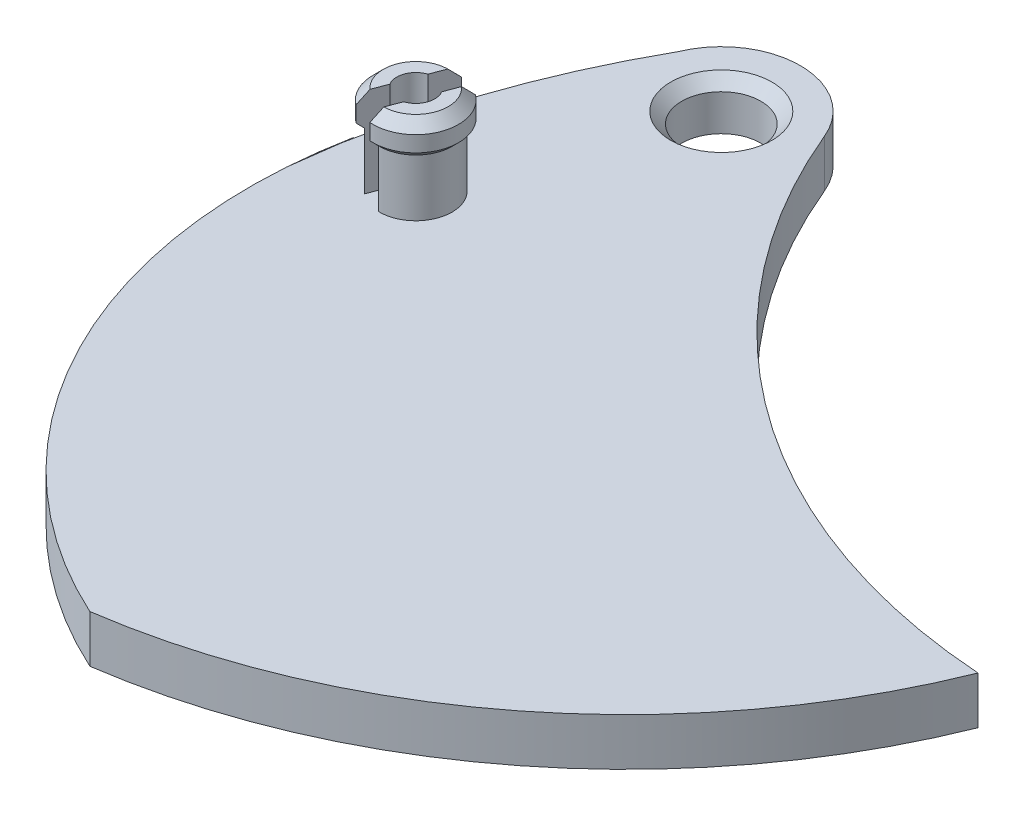
SolidWorks part; units mm, degrees
ref_plane "Front Plane" through (0, 0, 0) normal (0, 0, 1) x (1, 0, 0)
ref_plane "Top Plane" through (0, 0, 0) normal (0, 1, 0) x (1, 0, 0)
ref_plane "Right Plane" through (0, 0, 0) normal (1, 0, 0) x (0, 0, -1)
sketch "Sketch1" plane through (0, 0, 0) normal (0, 1, 0) x (1, 0, 0)
  line L5 (36.4058, -26.4503) -> (51.1392, -23.6349) construction
  line L6 (36.4058, 26.4503) -> (25.6898, 36.9464) construction
  line L7 (-9.9393, 38.7454) -> (25.6898, 36.9464) construction
  line L8 (-45, 0) -> (-50.2845, -14.0383) construction
  line L9 (0, 0) -> (25.6898, 36.9464) construction
  line L10 (-50.2845, -14.0383) -> (-37.5654, -47.3684) construction
  line L11 (-6.1164, -22.6509) -> (-50.2845, -14.0383) construction
  line L12 (51.1392, -23.6349) -> (35.4442, 18.5394) construction
  line L13 (51.1392, -23.6349) -> (72.9384, 4.6045) construction
  line L14 (51.1392, -23.6349) -> (45.5911, -53.1174) construction
  line L15 (-69.4092, 9.0754) -> (-50.2845, -14.0383) construction
  line L16 (-69.4092, 9.0754) -> (0, 0) construction
  line L17 (36.4058, -26.4503) -> (0, 0) construction
  line L18 (36.4058, 26.4503) -> (0, 0) construction
  line L19 (45.5911, -53.1174) -> (0, 0) construction
  line L20 (25.6898, 36.9464) -> (55.0124, 43.2856) construction
  line L21 (55.0124, 43.2856) -> (0, 0) construction
  line L22 (51.1392, -23.6349) -> (34.7485, -11.7263) construction
  line L23 (25.6898, 36.9464) -> (9.2991, 25.0379) construction
  circle A12 centre (25.6898, 36.9464) radius 2.5 construction
  circle A15 centre (25.6898, 36.9464) radius 5 construction
  circle A16 centre (-13.9058, 42.7975) radius 2.5
  circle A19 centre (-13.9058, 42.7975) radius 5
  circle A26 centre (0, 0) radius 40
  circle A27 centre (0, 0) radius 50 construction
  circle A28 centre (-45, 0) radius 5
  circle A29 centre (-45, 0) radius 2.5
  arc A38 (-40.3824, 1.9177) -> (-6.1164, -22.6509) centre (-3.4415, 17.2596) ccw
  circle A39 centre (-50.2845, -14.0383) radius 2.5
  circle A40 centre (-50.2845, -14.0383) radius 5
  arc A41 (-6.1164, -22.6509) -> (-37.5654, -47.3684) centre (-43.2469, -7.774) cw
  arc A42 (-55.1921, -13.0814) -> (-37.5654, -47.3684) centre (-24.6254, -19.0417) ccw
  arc A43 (-49.6161, 1.9214) -> (-55.2764, -13.7547) centre (-6.0759, -22.6602) ccw
  circle A44 centre (-69.4092, 9.0754) radius 2.5
  circle A45 centre (-69.4092, 9.0754) radius 5
  circle A46 centre (0, 0) radius 2.5 construction
  circle A47 centre (0, 0) radius 5 construction
  circle A48 centre (0, 0) radius 80 construction
  circle A49 centre (0, 0) radius 65
  circle A50 centre (36.4058, 26.4503) radius 2.5
  circle A51 centre (36.4058, 26.4503) radius 5
  circle A52 centre (36.4058, -26.4503) radius 2.5
  circle A53 centre (36.4058, -26.4503) radius 5
  circle A54 centre (-13.9058, -42.7975) radius 2.5
  circle A55 centre (-13.9058, -42.7975) radius 5
  arc A60 (36.2989, 21.4515) -> (0, 0) centre (35.4442, -18.5394) ccw construction
  arc A61 (40.4508, 29.3893) -> (28.5442, 41.0516) centre (0, 0) ccw construction
  arc A62 (-9.9393, 38.7454) -> (0, 0) centre (28.5849, 27.9804) ccw construction
  arc A63 (-9.9393, 38.7454) -> (28.5442, 41.0516) centre (10.7655, 15.4827) cw construction
  arc A66 (35.4442, 18.5394) -> (32.3607, -23.5114) centre (0, 0) cw construction
  arc A67 (35.4442, 18.5394) -> (72.9384, 4.6045) centre (42.1233, -20.899) cw construction
  circle A68 centre (51.1392, -23.6349) radius 5 construction
  circle A69 centre (51.1392, -23.6349) radius 2.5 construction
  arc A70 (72.9384, 4.6045) -> (52.8831, -28.3209) centre (42.0213, 0.8659) cw construction
  arc A71 (52.8831, -28.3209) -> (36.5126, -31.4492) centre (35.4442, 18.5394) cw construction
  circle A72 centre (45.5911, -53.1174) radius 2.5 construction
  circle A73 centre (45.5911, -53.1174) radius 5 construction
  circle A74 centre (55.0124, 43.2856) radius 2.5 construction
  circle A75 centre (55.0124, 43.2856) radius 5 construction
  point P80 (-40, 0)
  dimension "D5" = 2.197
  dimension "D9" = 15
  dimension "D16" = 10
  dimension "D17" = 5
  dimension "D19" = 80
  dimension "D23" = 2.197
  dimension "D20" = 45
  dimension "D13" = 160
  dimension "D4" = 45
  dimension "D6" = 13.36
  dimension "D7" = 226.818
  dimension "D8" = 115.343
  dimension "D10" = 30
  dimension "D11" = 70
  dimension "D12" = 45
  dimension "D14" = 166.64
  dimension "D15" = 30
  dimension "D18" = 15
  dimension "D21" = 70
  dimension "D22" = 279.594
  dimension "D26" = 15
  dimension "D27" = 30
  dimension "D28" = 70
  dimension "D29" = 249.372
  dimension "D3" = 5
extrude "Boss-Extrude2" add sketch "Sketch1" against normal blind 3 contours A28 A29 | A28 A43 A40 A42 A41 A26 | A41 A38 A26 | A40 A43 A39 | A38 A28 A26 | A39 region at (-23.7639, 0, 22.3313) region at (-40.0732, 0, -0.9824) region at (-45.952, 0, 4.7644) region at (-39.5577, 0, 28.1284) region at (-49.4902, 0, 9.2451)
sketch "Sketch2" plane through (0, 0, 0) normal (0, 1, 0) x (1, 0, 0)
  line L0 (-50.2845, -14.0383) -> (-45, 0) construction
  line L1 (-50.2845, -14.0383) -> (-6.1164, -22.6509) construction
  line L2 (-47.4547, -8.295) -> (-50.5523, -16.5239) construction
  line L3 (-48.6246, -7.8547) -> (-51.7222, -16.0835) construction
  line L4 (-47.4547, -8.295) -> (-48.0396, -8.0749) construction
  line L5 (-48.0396, -8.0749) -> (-48.6246, -7.8547) construction
  circle A0 centre (-50.2845, -14.0383) radius 5 construction
  circle A1 centre (-50.2845, -14.0383) radius 2.5 construction
  circle A4 centre (-50.2845, -14.0383) radius 2.3
  dimension "D1" = 5
  dimension "D2" = 10
  dimension "D4" = 4.6
  dimension "D3" = 15
  dimension "D5" = 45
  dimension "D6" = 1.25
extrude "Boss-Extrude3" add sketch "Sketch2" along normal blind 4
sketch "Sketch3" plane through (0, 4, 0) normal (0, 1, 0) x (1, 0, 0)
  circle A0 centre (-50.2845, -14.0383) radius 2.7
  dimension "D1" = 5.4
extrude "Boss-Extrude4" add sketch "Sketch3" along normal blind 1
chamfer "Chamfer1" distance 0.4 1 edges at (-50.2845, 4, 16.3383)
sketch "Sketch4" plane through (0, 5, 0) normal (0, 1, 0) x (1, 0, 0)
  circle A0 centre (-50.2845, -14.0383) radius 2.05
  circle A1 centre (-50.2845, -14.0383) radius 2.7 construction
  dimension "D1" = 4.1
extrude "Boss-Extrude5" add sketch "Sketch4" along normal blind 0.65
chamfer "Chamfer2" distance 0.65 1 edges at (-50.2845, 5, 16.0883)
sketch "Sketch5" plane through (0, 0, 0) normal (0, 1, 0) x (1, 0, 0)
sketch "Sketch6" plane through (0, 5.65, 0) normal (0, 1, 0) x (1, 0, 0)
  line L0 (-45, 0) -> (-50.2845, -14.0383) construction
  line L1 (-45, 0) -> (-44.2981, -0.2642) construction
  line L2 (-44.2981, -0.2642) -> (-51.3241, -18.929)
  line L3 (-45, 0) -> (-45.7019, 0.2642) construction
  line L4 (-45.7019, 0.2642) -> (-52.728, -18.4006)
  circle A0 centre (-45, 0) radius 2.5
  circle A1 centre (-45, 0) radius 2.5 construction
  circle A2 centre (-50.2845, -14.0383) radius 2.05
  circle A3 centre (-50.2845, -14.0383) radius 5
  circle M9 centre (-50.2845, -14.0383) radius 2.05
  dimension "D2" = 10
  dimension "D1" = 1.5
extrude "Cut-Extrude1" cut sketch "Sketch6" against normal up to surface (5.65 mm away) contours L4 L2 M9 | L2 A3 L4 M9 | L4 A3 L2 M9 region at (-49.0543, 5.65, 10.7702) region at (-50.2845, 5.65, 14.0383) region at (-51.5147, 5.65, 17.3064) up to face at (-50.2845, 0, 16.3383)
sketch "Sketch7" plane through (0, 5.65, 0) normal (0, 1, 0) x (1, 0, 0)
  circle A0 centre (-50.2845, -14.0383) radius 1.2
  dimension "D1" = 2.4
extrude "Cut-Extrude2" cut sketch "Sketch7" against normal up to surface (5.65 mm away) up to face at (-48.8573, 0, 14.5756)
chamfer "Chamfer3" distance 0.7 angle 45 1 edges at (-45, 0, 2.5)
